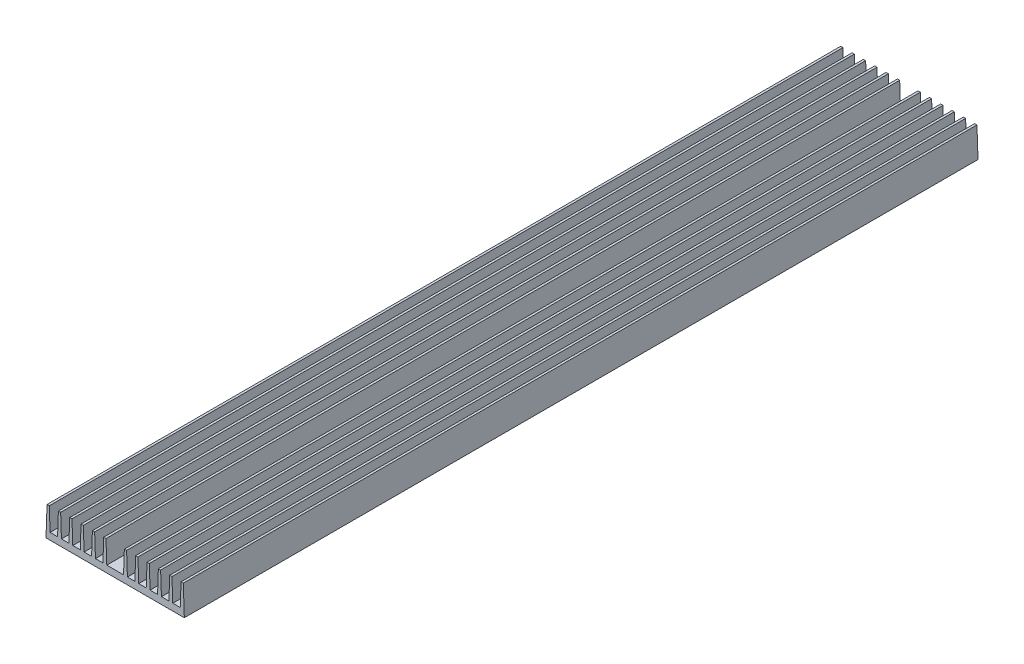
SolidWorks part; units mm, degrees
material "1060 Alloy"
ref_plane "Front Plane" through (0, 0, 0) normal (0, 0, 1) x (1, 0, 0)
ref_plane "Top Plane" through (0, 0, 0) normal (0, 1, 0) x (1, 0, 0)
ref_plane "Right Plane" through (0, 0, 0) normal (1, 0, 0) x (0, 0, -1)
sketch "Sketch1" plane through (0, 0, 0) normal (0, 0, 1) x (1, 0, 0)
  line L0 (61, 0) -> (-61, 0)
  line L1 (-61, 0) -> (-60.0921, 26)
  line L2 (-60.0921, 26) -> (-58.0921, 26)
  line L3 (-58.0921, 26) -> (-57.3936, 6)
  line L4 (-57.3936, 6) -> (-50.7905, 6)
  line L5 (0, 0) -> (0, 1.7954) construction
  line L6 (0, 0) -> (0, 37.7161) construction
  line L7 (-59.0921, 26) -> (-59.0921, 4.3612) construction
  line L8 (-50.0921, 26) -> (-48.0921, 26)
  line L9 (-48.0921, 26) -> (-47.3936, 6)
  line L10 (-50.7905, 6) -> (-50.0921, 26)
  line L11 (-40.0921, 26) -> (-38.0921, 26)
  line L12 (-38.0921, 26) -> (-37.3936, 6)
  line L13 (-40.7905, 6) -> (-40.0921, 26)
  line L14 (-30.0921, 26) -> (-28.0921, 26)
  line L15 (-28.0921, 26) -> (-27.3936, 6)
  line L16 (-30.7905, 6) -> (-30.0921, 26)
  line L17 (-27.3936, 6) -> (-20.7905, 6)
  line L18 (-37.3936, 6) -> (-30.7905, 6)
  line L19 (-47.3936, 6) -> (-40.7905, 6)
  line L20 (47.3936, 6) -> (40.7905, 6)
  line L21 (37.3936, 6) -> (30.7905, 6)
  line L22 (30.7905, 6) -> (30.0921, 26)
  line L23 (28.0921, 26) -> (27.3936, 6)
  line L24 (30.0921, 26) -> (28.0921, 26)
  line L25 (40.7905, 6) -> (40.0921, 26)
  line L26 (38.0921, 26) -> (37.3936, 6)
  line L27 (40.0921, 26) -> (38.0921, 26)
  line L28 (50.7905, 6) -> (50.0921, 26)
  line L29 (48.0921, 26) -> (47.3936, 6)
  line L30 (50.0921, 26) -> (48.0921, 26)
  line L31 (57.3936, 6) -> (50.7905, 6)
  line L32 (58.0921, 26) -> (57.3936, 6)
  line L33 (60.0921, 26) -> (58.0921, 26)
  line L34 (61, 0) -> (60.0921, 26)
  line L35 (-20.0921, 26) -> (-18.0921, 26)
  line L36 (-18.0921, 26) -> (-17.3936, 6)
  line L37 (-20.7905, 6) -> (-20.0921, 26)
  line L38 (-10.0921, 26) -> (-8.0921, 26)
  line L39 (-8.0921, 26) -> (-7.3936, 6)
  line L40 (-10.7905, 6) -> (-10.0921, 26)
  line L41 (-17.3936, 6) -> (-10.7905, 6)
  line L42 (-7.3936, 6) -> (7.3936, 6)
  line L43 (17.3936, 6) -> (10.7905, 6)
  line L44 (10.7905, 6) -> (10.0921, 26)
  line L45 (8.0921, 26) -> (7.3936, 6)
  line L46 (10.0921, 26) -> (8.0921, 26)
  line L47 (20.7905, 6) -> (20.0921, 26)
  line L48 (18.0921, 26) -> (17.3936, 6)
  line L49 (20.0921, 26) -> (18.0921, 26)
  line L51 (20.7905, 6) -> (27.3936, 6)
  point P3 (-59.0921, 26)
  point P29 (0, 6)
  dimension "D1" = 26
  dimension "D2" = 20
  dimension "D3" = 122
  dimension "D4" = 4
  dimension "D5" = 2
  dimension "D6" = 6
extrude "Boss-Extrude1" add sketch "Sketch1" along normal blind 350 and the other way blind 350
